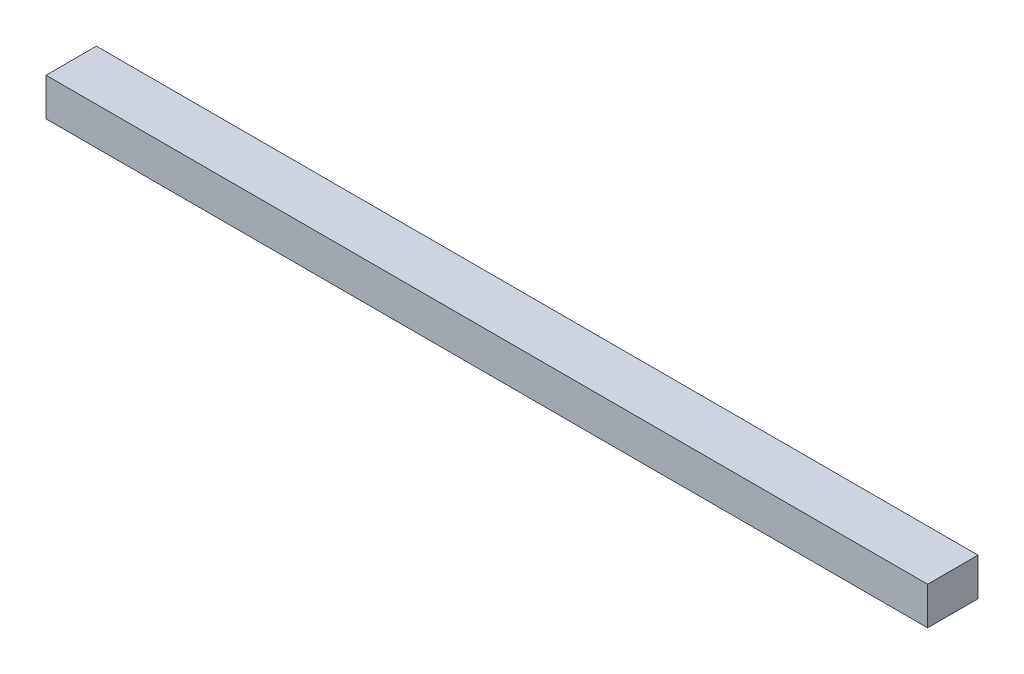
SolidWorks part; units mm, degrees
material "Maple"
ref_plane "Front Plane" through (0, 0, 0) normal (0, 0, 1) x (1, 0, 0)
ref_plane "Top Plane" through (0, 0, 0) normal (0, 1, 0) x (1, 0, 0)
ref_plane "Right Plane" through (0, 0, 0) normal (1, 0, 0) x (0, 0, -1)
sketch "Sketch1" plane through (0, 0, 0) normal (0, 1, 0) x (1, 0, 0)
  line L1 (0, 0) -> (140, 0)
  line L2 (0, 0) -> (0, 8)
  line L3 (0, 8) -> (140, 8)
  line L4 (140, 0) -> (140, 8)
  dimension "D1" = 8
extrude "Boss-Extrude1" add sketch "Sketch1" along normal blind 6
ref_plane "Plane1" through (0, 3, 0) normal (0, 1, 0) x (1, 0, 0)
